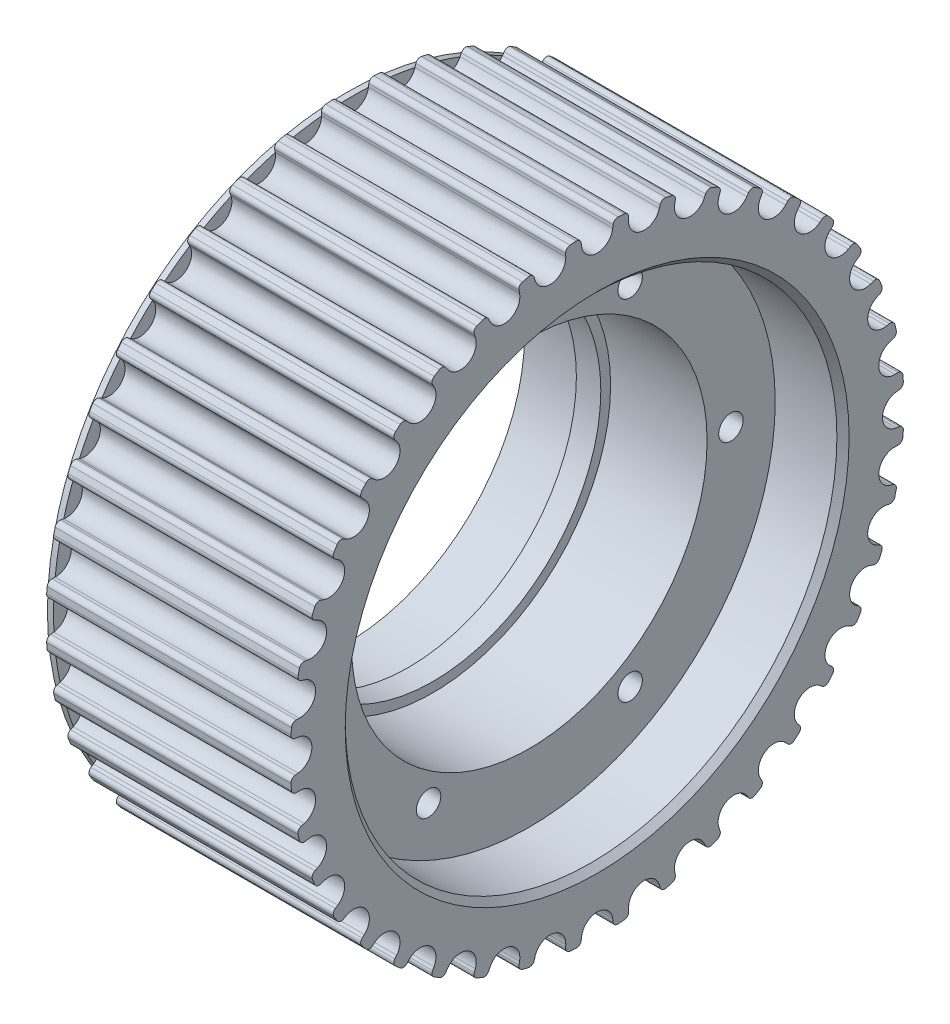
SolidWorks part; units mm, degrees
ref_plane "前视基准面" through (0, 0, 0) normal (0, 0, 1) x (1, 0, 0)
ref_plane "上视基准面" through (0, 0, 0) normal (0, 1, 0) x (1, 0, 0)
ref_plane "右视基准面" through (0, 0, 0) normal (1, 0, 0) x (0, 0, -1)
sketch "草图1" plane through (0, 0, 0) normal (0, 0, 1) x (1, 0, 0)
  line L0 (0, 0) -> (64.8368, 0) construction
  line L1 (0, 10.0488) -> (0, 50.244)
  line L2 (0, 50.244) -> (28, 50.244)
  line L3 (28, 50.244) -> (28, 20.0976)
  line L4 (28, 20.0976) -> (20, 20.0976)
  line L5 (20, 20.0976) -> (20, 10.0488)
  line L6 (20, 10.0488) -> (0, 10.0488)
  dimension "L" = 20
  dimension "B" = 28
  dimension "d" = 20.0976
  dimension "d1" = 40.1952
  dimension "da" = 100.488
revolve "旋转1" add sketch "草图1" angle 360 about L0
chamfer "倒角1" distance 1 angle 45 2 edges at (20, 0, 10.0488) (0, 0, 10.0488)
sketch "草图4" plane through (0, 0, 0) normal (-1, 0, 0) x (0, 0, 1)
  line L1 (-3, 9.5905) -> (3, 9.5905)
  line L2 (-3, 9.5905) -> (-3, 12.3905)
  line L3 (-3, 12.3905) -> (3, 12.3905)
  line L4 (3, 9.5905) -> (3, 12.3905)
  circle A0 centre (0, 0) radius 10.0488 construction
  dimension "键槽宽度" = 6
  dimension "t1" = 2.8
extrude "切除-拉伸1" cut sketch "草图4" against normal through all
ref_axis "基准轴1" through (-1.4, 0, 0) along (1, 0, 0)
sketch "草图6" plane through (0, 0, 0) normal (1, 0, 0) x (0, 0, -1)
  line L0 (0, 0) -> (0, 30.6512) construction
  line L1 (2.6101, 49.4431) -> (2.5508, 48.9608)
  line L2 (4.2154, 50.0669) -> (4.412, 51.6684)
  line L3 (-4.2154, 50.0669) -> (-4.412, 51.6684)
  line L4 (-2.6101, 49.4431) -> (-2.5508, 48.9608)
  circle A0 centre (0, 0) radius 50.244 construction
  circle A1 centre (0, 0) radius 46.704 construction
  arc A2 (-2.5508, 48.9608) -> (2.5508, 48.9608) centre (0, 49.274) ccw
  arc A3 (4.412, 51.6684) -> (-4.412, 51.6684) centre (0, 0) ccw
  arc A4 (2.6101, 49.4431) -> (3.4376, 50.1263) centre (3.3843, 49.3481) cw
  arc A5 (3.4376, 50.1263) -> (4.2154, 50.0669) centre (0, 0) cw
  arc A6 (-3.4376, 50.1263) -> (-4.2154, 50.0669) centre (0, 0) ccw
  arc A7 (-2.6101, 49.4431) -> (-3.4376, 50.1263) centre (-3.3843, 49.3481) ccw
  point P7 (0, 5.35)
  point P8 (0, 27.1112)
  point P15 (2.6995, 50.1714)
  dimension "D1" = 93.408
  dimension "ra" = 0.78
  dimension "rf" = 2.57
  dimension "hg" = 3.54
  dimension "D3" = 0.78
  dimension "D4" = 1.6136
  dimension "angle" = 14
  dimension "bw" = 5.35
extrude "切除-拉伸2" cut sketch "草图6" along normal up to next
pattern_circular "阵列(圆周)3" count 40 over 360 about axis through (-1.4, 0, 0) along (1, 0, 0) of "切除-拉伸2"
sketch "草图7" plane through (0, 0, 0) normal (-1, 0, 0) x (0, 0, 1)
  line L80 (-5.1567, 49.2427) -> (-5.1397, 48.757)
  line L81 (-10.1786, 47.959) -> (-10.3125, 48.4261)
  line L82 (-12.7965, 47.8298) -> (-12.7037, 47.3527)
  line L83 (-17.5557, 45.7762) -> (-17.7611, 46.2167)
  line L84 (-20.1211, 45.2391) -> (-19.9549, 44.7824)
  line L85 (-24.5006, 42.4663) -> (-24.7723, 42.8692)
  line L86 (-26.9504, 41.5345) -> (-26.7148, 41.1095)
  line L87 (-30.8421, 38.1108) -> (-31.1735, 38.4662)
  line L88 (-33.116, 36.8072) -> (-32.8168, 36.4242)
  line L89 (-36.4242, 32.8168) -> (-36.8072, 33.116)
  line L90 (-38.4662, 31.1735) -> (-38.1108, 30.8421)
  line L91 (-41.1095, 26.7148) -> (-41.5345, 26.9504)
  line L92 (-42.8692, 24.7723) -> (-42.4663, 24.5006)
  line L93 (-44.7824, 19.9549) -> (-45.2391, 20.1211)
  line L94 (-46.2167, 17.7611) -> (-45.7762, 17.5557)
  line L95 (-47.3527, 12.7037) -> (-47.8298, 12.7965)
  line L96 (-48.4261, 10.3125) -> (-47.959, 10.1786)
  line L97 (-48.757, 5.1397) -> (-49.2427, 5.1567)
  line L98 (-49.4431, 2.6101) -> (-48.9608, 2.5508)
  line L99 (-48.9608, -2.5508) -> (-49.4431, -2.6101)
  line L100 (-49.2427, -5.1567) -> (-48.757, -5.1397)
  line L101 (-47.959, -10.1786) -> (-48.4261, -10.3125)
  line L102 (-47.8298, -12.7965) -> (-47.3527, -12.7037)
  line L103 (-45.7762, -17.5557) -> (-46.2167, -17.7611)
  line L104 (-45.2391, -20.1211) -> (-44.7824, -19.9549)
  line L105 (-42.4663, -24.5006) -> (-42.8692, -24.7723)
  line L106 (-41.5345, -26.9504) -> (-41.1095, -26.7148)
  line L107 (-38.1108, -30.8421) -> (-38.4662, -31.1735)
  line L108 (-36.8072, -33.116) -> (-36.4242, -32.8168)
  line L109 (-32.8168, -36.4242) -> (-33.116, -36.8072)
  line L110 (-31.1735, -38.4662) -> (-30.8421, -38.1108)
  line L111 (-26.7148, -41.1095) -> (-26.9504, -41.5345)
  line L112 (-24.7723, -42.8692) -> (-24.5006, -42.4663)
  line L113 (-19.9549, -44.7824) -> (-20.1211, -45.2391)
  line L114 (-17.7611, -46.2167) -> (-17.5557, -45.7762)
  line L115 (-12.7037, -47.3527) -> (-12.7965, -47.8298)
  line L116 (-10.3125, -48.4261) -> (-10.1786, -47.959)
  line L117 (-5.1397, -48.757) -> (-5.1567, -49.2427)
  line L118 (-2.6101, -49.4431) -> (-2.5508, -48.9608)
  line L119 (2.5508, -48.9608) -> (2.6101, -49.4431)
  line L120 (5.1567, -49.2427) -> (5.1397, -48.757)
  line L121 (10.1786, -47.959) -> (10.3125, -48.4261)
  line L122 (12.7965, -47.8298) -> (12.7037, -47.3527)
  line L123 (17.5557, -45.7762) -> (17.7611, -46.2167)
  line L124 (20.1211, -45.2391) -> (19.9549, -44.7824)
  line L125 (24.5006, -42.4663) -> (24.7723, -42.8692)
  line L126 (26.9504, -41.5345) -> (26.7148, -41.1095)
  line L127 (30.8421, -38.1108) -> (31.1735, -38.4662)
  line L128 (33.116, -36.8072) -> (32.8168, -36.4242)
  line L129 (36.4242, -32.8168) -> (36.8072, -33.116)
  line L130 (38.4662, -31.1735) -> (38.1108, -30.8421)
  line L131 (41.1095, -26.7148) -> (41.5345, -26.9504)
  line L132 (42.8692, -24.7723) -> (42.4663, -24.5006)
  line L133 (44.7824, -19.9549) -> (45.2391, -20.1211)
  line L134 (46.2167, -17.7611) -> (45.7762, -17.5557)
  line L135 (47.3527, -12.7037) -> (47.8298, -12.7965)
  line L136 (48.4261, -10.3125) -> (47.959, -10.1786)
  line L137 (48.757, -5.1397) -> (49.2427, -5.1567)
  line L138 (49.4431, -2.6101) -> (48.9608, -2.5508)
  line L139 (48.9608, 2.5508) -> (49.4431, 2.6101)
  line L140 (49.2427, 5.1567) -> (48.757, 5.1397)
  line L141 (47.959, 10.1786) -> (48.4261, 10.3125)
  line L142 (47.8298, 12.7965) -> (47.3527, 12.7037)
  line L143 (45.7762, 17.5557) -> (46.2167, 17.7611)
  line L144 (45.2391, 20.1211) -> (44.7824, 19.9549)
  line L145 (42.4663, 24.5006) -> (42.8692, 24.7723)
  line L146 (41.5345, 26.9504) -> (41.1095, 26.7148)
  line L147 (38.1108, 30.8421) -> (38.4662, 31.1735)
  line L148 (36.8072, 33.116) -> (36.4242, 32.8168)
  line L149 (32.8168, 36.4242) -> (33.116, 36.8072)
  line L150 (31.1735, 38.4662) -> (30.8421, 38.1108)
  line L151 (26.7148, 41.1095) -> (26.9504, 41.5345)
  line L152 (24.7723, 42.8692) -> (24.5006, 42.4663)
  line L153 (19.9549, 44.7824) -> (20.1211, 45.2391)
  line L154 (17.7611, 46.2167) -> (17.5557, 45.7762)
  line L155 (12.7037, 47.3527) -> (12.7965, 47.8298)
  line L156 (10.3125, 48.4261) -> (10.1786, 47.959)
  line L157 (5.1397, 48.757) -> (5.1567, 49.2427)
  line L158 (2.6101, 49.4431) -> (2.5508, 48.9608)
  line L159 (-2.5508, 48.9608) -> (-2.6101, 49.4431)
  line L160 (-5.1567, 49.2427) -> (-5.1397, 48.757)
  line L161 (-10.1786, 47.959) -> (-10.3125, 48.4261)
  line L162 (-12.7965, 47.8298) -> (-12.7037, 47.3527)
  line L163 (-17.5557, 45.7762) -> (-17.7611, 46.2167)
  line L164 (-20.1211, 45.2391) -> (-19.9549, 44.7824)
  line L165 (-24.5006, 42.4663) -> (-24.7723, 42.8692)
  line L166 (-26.9504, 41.5345) -> (-26.7148, 41.1095)
  line L167 (-30.8421, 38.1108) -> (-31.1735, 38.4662)
  line L168 (-33.116, 36.8072) -> (-32.8168, 36.4242)
  line L169 (-36.4242, 32.8168) -> (-36.8072, 33.116)
  line L170 (-38.4662, 31.1735) -> (-38.1108, 30.8421)
  line L171 (-41.1095, 26.7148) -> (-41.5345, 26.9504)
  line L172 (-42.8692, 24.7723) -> (-42.4663, 24.5006)
  line L173 (-44.7824, 19.9549) -> (-45.2391, 20.1211)
  line L174 (-46.2167, 17.7611) -> (-45.7762, 17.5557)
  line L175 (-47.3527, 12.7037) -> (-47.8298, 12.7965)
  line L176 (-48.4261, 10.3125) -> (-47.959, 10.1786)
  line L177 (-48.757, 5.1397) -> (-49.2427, 5.1567)
  line L178 (-49.4431, 2.6101) -> (-48.9608, 2.5508)
  line L179 (-48.9608, -2.5508) -> (-49.4431, -2.6101)
  line L180 (-49.2427, -5.1567) -> (-48.757, -5.1397)
  line L181 (-47.959, -10.1786) -> (-48.4261, -10.3125)
  line L182 (-47.8298, -12.7965) -> (-47.3527, -12.7037)
  line L183 (-45.7762, -17.5557) -> (-46.2167, -17.7611)
  line L184 (-45.2391, -20.1211) -> (-44.7824, -19.9549)
  line L185 (-42.4663, -24.5006) -> (-42.8692, -24.7723)
  line L186 (-41.5345, -26.9504) -> (-41.1095, -26.7148)
  line L187 (-38.1108, -30.8421) -> (-38.4662, -31.1735)
  line L188 (-36.8072, -33.116) -> (-36.4242, -32.8168)
  line L189 (-32.8168, -36.4242) -> (-33.116, -36.8072)
  line L190 (-31.1735, -38.4662) -> (-30.8421, -38.1108)
  line L191 (-26.7148, -41.1095) -> (-26.9504, -41.5345)
  line L192 (-24.7723, -42.8692) -> (-24.5006, -42.4663)
  line L193 (-19.9549, -44.7824) -> (-20.1211, -45.2391)
  line L194 (-17.7611, -46.2167) -> (-17.5557, -45.7762)
  line L195 (-12.7037, -47.3527) -> (-12.7965, -47.8298)
  line L196 (-10.3125, -48.4261) -> (-10.1786, -47.959)
  line L197 (-5.1397, -48.757) -> (-5.1567, -49.2427)
  line L198 (-2.6101, -49.4431) -> (-2.5508, -48.9608)
  line L199 (2.5508, -48.9608) -> (2.6101, -49.4431)
  line L200 (5.1567, -49.2427) -> (5.1397, -48.757)
  line L201 (10.1786, -47.959) -> (10.3125, -48.4261)
  line L202 (12.7965, -47.8298) -> (12.7037, -47.3527)
  line L203 (17.5557, -45.7762) -> (17.7611, -46.2167)
  line L204 (20.1211, -45.2391) -> (19.9549, -44.7824)
  line L205 (24.5006, -42.4663) -> (24.7723, -42.8692)
  line L206 (26.9504, -41.5345) -> (26.7148, -41.1095)
  line L207 (30.8421, -38.1108) -> (31.1735, -38.4662)
  line L208 (33.116, -36.8072) -> (32.8168, -36.4242)
  line L209 (36.4242, -32.8168) -> (36.8072, -33.116)
  line L210 (38.4662, -31.1735) -> (38.1108, -30.8421)
  line L211 (41.1095, -26.7148) -> (41.5345, -26.9504)
  line L212 (42.8692, -24.7723) -> (42.4663, -24.5006)
  line L213 (44.7824, -19.9549) -> (45.2391, -20.1211)
  line L214 (46.2167, -17.7611) -> (45.7762, -17.5557)
  line L215 (47.3527, -12.7037) -> (47.8298, -12.7965)
  line L216 (48.4261, -10.3125) -> (47.959, -10.1786)
  line L217 (48.757, -5.1397) -> (49.2427, -5.1567)
  line L218 (49.4431, -2.6101) -> (48.9608, -2.5508)
  line L219 (48.9608, 2.5508) -> (49.4431, 2.6101)
  line L220 (49.2427, 5.1567) -> (48.757, 5.1397)
  line L221 (47.959, 10.1786) -> (48.4261, 10.3125)
  line L222 (47.8298, 12.7965) -> (47.3527, 12.7037)
  line L223 (45.7762, 17.5557) -> (46.2167, 17.7611)
  line L224 (45.2391, 20.1211) -> (44.7824, 19.9549)
  line L225 (42.4663, 24.5006) -> (42.8692, 24.7723)
  line L226 (41.5345, 26.9504) -> (41.1095, 26.7148)
  line L227 (38.1108, 30.8421) -> (38.4662, 31.1735)
  line L228 (36.8072, 33.116) -> (36.4242, 32.8168)
  line L229 (32.8168, 36.4242) -> (33.116, 36.8072)
  line L230 (31.1735, 38.4662) -> (30.8421, 38.1108)
  line L231 (26.7148, 41.1095) -> (26.9504, 41.5345)
  line L232 (24.7723, 42.8692) -> (24.5006, 42.4663)
  line L233 (19.9549, 44.7824) -> (20.1211, 45.2391)
  line L234 (17.7611, 46.2167) -> (17.5557, 45.7762)
  line L235 (12.7037, 47.3527) -> (12.7965, 47.8298)
  line L236 (10.3125, 48.4261) -> (10.1786, 47.959)
  line L237 (5.1397, 48.757) -> (5.1567, 49.2427)
  line L238 (2.6101, 49.4431) -> (2.5508, 48.9608)
  line L239 (-2.5508, 48.9608) -> (-2.6101, 49.4431)
  arc A160 (-4.4462, 50.0469) -> (-5.1567, 49.2427) centre (-4.3772, 49.2699) ccw
  arc A161 (-10.1786, 47.959) -> (-5.1397, 48.757) centre (-7.7082, 48.6674) ccw
  arc A162 (-10.3125, 48.4261) -> (-11.2368, 48.9714) centre (-11.0623, 48.2111) ccw
  arc A163 (-11.2368, 48.9714) -> (-12.2205, 48.7352) centre (0, 0) ccw
  arc A164 (-12.2205, 48.7352) -> (-12.7965, 47.8298) centre (-12.0308, 47.9786) ccw
  arc A165 (-17.5557, 45.7762) -> (-12.7037, 47.3527) centre (-15.2265, 46.8624) ccw
  arc A166 (-17.7611, 46.2167) -> (-18.7592, 46.6106) centre (-18.468, 45.887) ccw
  arc A167 (-18.7592, 46.6106) -> (-19.6939, 46.2235) centre (0, 0) ccw
  arc A168 (-19.6939, 46.2235) -> (-20.1211, 45.2391) centre (-19.3882, 45.5059) ccw
  arc A169 (-24.5006, 42.4663) -> (-19.9549, 44.7824) centre (-22.3699, 43.9035) ccw
  arc A170 (-24.7723, 42.8692) -> (-25.8198, 43.1022) centre (-25.419, 42.4331) ccw
  arc A171 (-25.8198, 43.1022) -> (-26.6824, 42.5736) centre (0, 0) ccw
  arc A172 (-26.6824, 42.5736) -> (-26.9504, 41.5345) centre (-26.2682, 41.9127) ccw
  arc A173 (-30.8421, 38.1108) -> (-26.7148, 41.1095) centre (-28.9625, 39.8635) ccw
  arc A174 (-31.1735, 38.4662) -> (-32.2446, 38.5324) centre (-31.744, 37.9342) ccw
  arc A175 (-32.2446, 38.5324) -> (-33.0139, 37.8754) centre (0, 0) ccw
  arc A176 (-33.0139, 37.8754) -> (-33.116, 36.8072) centre (-32.5013, 37.2874) ccw
  arc A177 (-36.4242, 32.8168) -> (-32.8168, 36.4242) centre (-34.842, 34.842) ccw
  arc A178 (-36.8072, 33.116) -> (-37.8754, 33.0139) centre (-37.2874, 32.5013) ccw
  arc A179 (-37.8754, 33.0139) -> (-38.5324, 32.2446) centre (0, 0) ccw
  arc A180 (-38.5324, 32.2446) -> (-38.4662, 31.1735) centre (-37.9342, 31.744) ccw
  arc A181 (-41.1095, 26.7148) -> (-38.1108, 30.8421) centre (-39.8635, 28.9625) ccw
  arc A182 (-41.5345, 26.9504) -> (-42.5736, 26.6824) centre (-41.9127, 26.2682) ccw
  arc A183 (-42.5736, 26.6824) -> (-43.1022, 25.8198) centre (0, 0) ccw
  arc A184 (-43.1022, 25.8198) -> (-42.8692, 24.7723) centre (-42.4331, 25.419) ccw
  arc A185 (-44.7824, 19.9549) -> (-42.4663, 24.5006) centre (-43.9035, 22.3699) ccw
  arc A186 (-45.2391, 20.1211) -> (-46.2235, 19.6939) centre (-45.5059, 19.3882) ccw
  arc A187 (-46.2235, 19.6939) -> (-46.6106, 18.7592) centre (0, 0) ccw
  arc A188 (-46.6106, 18.7592) -> (-46.2167, 17.7611) centre (-45.887, 18.468) ccw
  arc A189 (-47.3527, 12.7037) -> (-45.7762, 17.5557) centre (-46.8624, 15.2265) ccw
  arc A190 (-47.8298, 12.7965) -> (-48.7352, 12.2205) centre (-47.9786, 12.0308) ccw
  arc A191 (-48.7352, 12.2205) -> (-48.9714, 11.2368) centre (0, 0) ccw
  arc A192 (-48.9714, 11.2368) -> (-48.4261, 10.3125) centre (-48.2111, 11.0623) ccw
  arc A193 (-48.757, 5.1397) -> (-47.959, 10.1786) centre (-48.6674, 7.7082) ccw
  arc A194 (-49.2427, 5.1567) -> (-50.0469, 4.4462) centre (-49.2699, 4.3772) ccw
  arc A195 (-50.0469, 4.4462) -> (-50.1263, 3.4376) centre (0, 0) ccw
  arc A196 (-50.1263, 3.4376) -> (-49.4431, 2.6101) centre (-49.3481, 3.3843) ccw
  arc A197 (-48.9608, -2.5508) -> (-48.9608, 2.5508) centre (-49.274, 0) ccw
  arc A198 (-49.4431, -2.6101) -> (-50.1263, -3.4376) centre (-49.3481, -3.3843) ccw
  arc A199 (-50.1263, -3.4376) -> (-50.0469, -4.4462) centre (0, 0) ccw
  arc A200 (-50.0469, -4.4462) -> (-49.2427, -5.1567) centre (-49.2699, -4.3772) ccw
  arc A201 (-47.959, -10.1786) -> (-48.757, -5.1397) centre (-48.6674, -7.7082) ccw
  arc A202 (-48.4261, -10.3125) -> (-48.9714, -11.2368) centre (-48.2111, -11.0623) ccw
  arc A203 (-48.9714, -11.2368) -> (-48.7352, -12.2205) centre (0, 0) ccw
  arc A204 (-48.7352, -12.2205) -> (-47.8298, -12.7965) centre (-47.9786, -12.0308) ccw
  arc A205 (-45.7762, -17.5557) -> (-47.3527, -12.7037) centre (-46.8624, -15.2265) ccw
  arc A206 (-46.2167, -17.7611) -> (-46.6106, -18.7592) centre (-45.887, -18.468) ccw
  arc A207 (-46.6106, -18.7592) -> (-46.2235, -19.6939) centre (0, 0) ccw
  arc A208 (-46.2235, -19.6939) -> (-45.2391, -20.1211) centre (-45.5059, -19.3882) ccw
  arc A209 (-42.4663, -24.5006) -> (-44.7824, -19.9549) centre (-43.9035, -22.3699) ccw
  arc A210 (-42.8692, -24.7723) -> (-43.1022, -25.8198) centre (-42.4331, -25.419) ccw
  arc A211 (-43.1022, -25.8198) -> (-42.5736, -26.6824) centre (0, 0) ccw
  arc A212 (-42.5736, -26.6824) -> (-41.5345, -26.9504) centre (-41.9127, -26.2682) ccw
  arc A213 (-38.1108, -30.8421) -> (-41.1095, -26.7148) centre (-39.8635, -28.9625) ccw
  arc A214 (-38.4662, -31.1735) -> (-38.5324, -32.2446) centre (-37.9342, -31.744) ccw
  arc A215 (-38.5324, -32.2446) -> (-37.8754, -33.0139) centre (0, 0) ccw
  arc A216 (-37.8754, -33.0139) -> (-36.8072, -33.116) centre (-37.2874, -32.5013) ccw
  arc A217 (-32.8168, -36.4242) -> (-36.4242, -32.8168) centre (-34.842, -34.842) ccw
  arc A218 (-33.116, -36.8072) -> (-33.0139, -37.8754) centre (-32.5013, -37.2874) ccw
  arc A219 (-33.0139, -37.8754) -> (-32.2446, -38.5324) centre (0, 0) ccw
  arc A220 (-32.2446, -38.5324) -> (-31.1735, -38.4662) centre (-31.744, -37.9342) ccw
  arc A221 (-26.7148, -41.1095) -> (-30.8421, -38.1108) centre (-28.9625, -39.8635) ccw
  arc A222 (-26.9504, -41.5345) -> (-26.6824, -42.5736) centre (-26.2682, -41.9127) ccw
  arc A223 (-26.6824, -42.5736) -> (-25.8198, -43.1022) centre (0, 0) ccw
  arc A224 (-25.8198, -43.1022) -> (-24.7723, -42.8692) centre (-25.419, -42.4331) ccw
  arc A225 (-19.9549, -44.7824) -> (-24.5006, -42.4663) centre (-22.3699, -43.9035) ccw
  arc A226 (-20.1211, -45.2391) -> (-19.6939, -46.2235) centre (-19.3882, -45.5059) ccw
  arc A227 (-19.6939, -46.2235) -> (-18.7592, -46.6106) centre (0, 0) ccw
  arc A228 (-18.7592, -46.6106) -> (-17.7611, -46.2167) centre (-18.468, -45.887) ccw
  arc A229 (-12.7037, -47.3527) -> (-17.5557, -45.7762) centre (-15.2265, -46.8624) ccw
  arc A230 (-12.7965, -47.8298) -> (-12.2205, -48.7352) centre (-12.0308, -47.9786) ccw
  arc A231 (-12.2205, -48.7352) -> (-11.2368, -48.9714) centre (0, 0) ccw
  arc A232 (-11.2368, -48.9714) -> (-10.3125, -48.4261) centre (-11.0623, -48.2111) ccw
  arc A233 (-5.1397, -48.757) -> (-10.1786, -47.959) centre (-7.7082, -48.6674) ccw
  arc A234 (-5.1567, -49.2427) -> (-4.4462, -50.0469) centre (-4.3772, -49.2699) ccw
  arc A235 (-4.4462, -50.0469) -> (-3.4376, -50.1263) centre (0, 0) ccw
  arc A236 (-3.4376, -50.1263) -> (-2.6101, -49.4431) centre (-3.3843, -49.3481) ccw
  arc A237 (2.5508, -48.9608) -> (-2.5508, -48.9608) centre (0, -49.274) ccw
  arc A238 (2.6101, -49.4431) -> (3.4376, -50.1263) centre (3.3843, -49.3481) ccw
  arc A239 (3.4376, -50.1263) -> (4.4462, -50.0469) centre (0, 0) ccw
  arc A240 (4.4462, -50.0469) -> (5.1567, -49.2427) centre (4.3772, -49.2699) ccw
  arc A241 (10.1786, -47.959) -> (5.1397, -48.757) centre (7.7082, -48.6674) ccw
  arc A242 (10.3125, -48.4261) -> (11.2368, -48.9714) centre (11.0623, -48.2111) ccw
  arc A243 (11.2368, -48.9714) -> (12.2205, -48.7352) centre (0, 0) ccw
  arc A244 (12.2205, -48.7352) -> (12.7965, -47.8298) centre (12.0308, -47.9786) ccw
  arc A245 (17.5557, -45.7762) -> (12.7037, -47.3527) centre (15.2265, -46.8624) ccw
  arc A246 (17.7611, -46.2167) -> (18.7592, -46.6106) centre (18.468, -45.887) ccw
  arc A247 (18.7592, -46.6106) -> (19.6939, -46.2235) centre (0, 0) ccw
  arc A248 (19.6939, -46.2235) -> (20.1211, -45.2391) centre (19.3882, -45.5059) ccw
  arc A249 (24.5006, -42.4663) -> (19.9549, -44.7824) centre (22.3699, -43.9035) ccw
  arc A250 (24.7723, -42.8692) -> (25.8198, -43.1022) centre (25.419, -42.4331) ccw
  arc A251 (25.8198, -43.1022) -> (26.6824, -42.5736) centre (0, 0) ccw
  arc A252 (26.6824, -42.5736) -> (26.9504, -41.5345) centre (26.2682, -41.9127) ccw
  arc A253 (30.8421, -38.1108) -> (26.7148, -41.1095) centre (28.9625, -39.8635) ccw
  arc A254 (31.1735, -38.4662) -> (32.2446, -38.5324) centre (31.744, -37.9342) ccw
  arc A255 (32.2446, -38.5324) -> (33.0139, -37.8754) centre (0, 0) ccw
  arc A256 (33.0139, -37.8754) -> (33.116, -36.8072) centre (32.5013, -37.2874) ccw
  arc A257 (36.4242, -32.8168) -> (32.8168, -36.4242) centre (34.842, -34.842) ccw
  arc A258 (36.8072, -33.116) -> (37.8754, -33.0139) centre (37.2874, -32.5013) ccw
  arc A259 (37.8754, -33.0139) -> (38.5324, -32.2446) centre (0, 0) ccw
  arc A260 (38.5324, -32.2446) -> (38.4662, -31.1735) centre (37.9342, -31.744) ccw
  arc A261 (41.1095, -26.7148) -> (38.1108, -30.8421) centre (39.8635, -28.9625) ccw
  arc A262 (41.5345, -26.9504) -> (42.5736, -26.6824) centre (41.9127, -26.2682) ccw
  arc A263 (42.5736, -26.6824) -> (43.1022, -25.8198) centre (0, 0) ccw
  arc A264 (43.1022, -25.8198) -> (42.8692, -24.7723) centre (42.4331, -25.419) ccw
  arc A265 (44.7824, -19.9549) -> (42.4663, -24.5006) centre (43.9035, -22.3699) ccw
  arc A266 (45.2391, -20.1211) -> (46.2235, -19.6939) centre (45.5059, -19.3882) ccw
  arc A267 (46.2235, -19.6939) -> (46.6106, -18.7592) centre (0, 0) ccw
  arc A268 (46.6106, -18.7592) -> (46.2167, -17.7611) centre (45.887, -18.468) ccw
  arc A269 (47.3527, -12.7037) -> (45.7762, -17.5557) centre (46.8624, -15.2265) ccw
  arc A270 (47.8298, -12.7965) -> (48.7352, -12.2205) centre (47.9786, -12.0308) ccw
  arc A271 (48.7352, -12.2205) -> (48.9714, -11.2368) centre (0, 0) ccw
  arc A272 (48.9714, -11.2368) -> (48.4261, -10.3125) centre (48.2111, -11.0623) ccw
  arc A273 (48.757, -5.1397) -> (47.959, -10.1786) centre (48.6674, -7.7082) ccw
  arc A274 (49.2427, -5.1567) -> (50.0469, -4.4462) centre (49.2699, -4.3772) ccw
  arc A275 (50.0469, -4.4462) -> (50.1263, -3.4376) centre (0, 0) ccw
  arc A276 (50.1263, -3.4376) -> (49.4431, -2.6101) centre (49.3481, -3.3843) ccw
  arc A277 (48.9608, 2.5508) -> (48.9608, -2.5508) centre (49.274, 0) ccw
  arc A278 (49.4431, 2.6101) -> (50.1263, 3.4376) centre (49.3481, 3.3843) ccw
  arc A279 (50.1263, 3.4376) -> (50.0469, 4.4462) centre (0, 0) ccw
  arc A280 (50.0469, 4.4462) -> (49.2427, 5.1567) centre (49.2699, 4.3772) ccw
  arc A281 (47.959, 10.1786) -> (48.757, 5.1397) centre (48.6674, 7.7082) ccw
  arc A282 (48.4261, 10.3125) -> (48.9714, 11.2368) centre (48.2111, 11.0623) ccw
  arc A283 (48.9714, 11.2368) -> (48.7352, 12.2205) centre (0, 0) ccw
  arc A284 (48.7352, 12.2205) -> (47.8298, 12.7965) centre (47.9786, 12.0308) ccw
  arc A285 (45.7762, 17.5557) -> (47.3527, 12.7037) centre (46.8624, 15.2265) ccw
  arc A286 (46.2167, 17.7611) -> (46.6106, 18.7592) centre (45.887, 18.468) ccw
  arc A287 (46.6106, 18.7592) -> (46.2235, 19.6939) centre (0, 0) ccw
  arc A288 (46.2235, 19.6939) -> (45.2391, 20.1211) centre (45.5059, 19.3882) ccw
  arc A289 (42.4663, 24.5006) -> (44.7824, 19.9549) centre (43.9035, 22.3699) ccw
  arc A290 (42.8692, 24.7723) -> (43.1022, 25.8198) centre (42.4331, 25.419) ccw
  arc A291 (43.1022, 25.8198) -> (42.5736, 26.6824) centre (0, 0) ccw
  arc A292 (42.5736, 26.6824) -> (41.5345, 26.9504) centre (41.9127, 26.2682) ccw
  arc A293 (38.1108, 30.8421) -> (41.1095, 26.7148) centre (39.8635, 28.9625) ccw
  arc A294 (38.4662, 31.1735) -> (38.5324, 32.2446) centre (37.9342, 31.744) ccw
  arc A295 (38.5324, 32.2446) -> (37.8754, 33.0139) centre (0, 0) ccw
  arc A296 (37.8754, 33.0139) -> (36.8072, 33.116) centre (37.2874, 32.5013) ccw
  arc A297 (32.8168, 36.4242) -> (36.4242, 32.8168) centre (34.842, 34.842) ccw
  arc A298 (33.116, 36.8072) -> (33.0139, 37.8754) centre (32.5013, 37.2874) ccw
  arc A299 (33.0139, 37.8754) -> (32.2446, 38.5324) centre (0, 0) ccw
  arc A300 (32.2446, 38.5324) -> (31.1735, 38.4662) centre (31.744, 37.9342) ccw
  arc A301 (26.7148, 41.1095) -> (30.8421, 38.1108) centre (28.9625, 39.8635) ccw
  arc A302 (26.9504, 41.5345) -> (26.6824, 42.5736) centre (26.2682, 41.9127) ccw
  arc A303 (26.6824, 42.5736) -> (25.8198, 43.1022) centre (0, 0) ccw
  arc A304 (25.8198, 43.1022) -> (24.7723, 42.8692) centre (25.419, 42.4331) ccw
  arc A305 (19.9549, 44.7824) -> (24.5006, 42.4663) centre (22.3699, 43.9035) ccw
  arc A306 (20.1211, 45.2391) -> (19.6939, 46.2235) centre (19.3882, 45.5059) ccw
  arc A307 (19.6939, 46.2235) -> (18.7592, 46.6106) centre (0, 0) ccw
  arc A308 (18.7592, 46.6106) -> (17.7611, 46.2167) centre (18.468, 45.887) ccw
  arc A309 (12.7037, 47.3527) -> (17.5557, 45.7762) centre (15.2265, 46.8624) ccw
  arc A310 (12.7965, 47.8298) -> (12.2205, 48.7352) centre (12.0308, 47.9786) ccw
  arc A311 (12.2205, 48.7352) -> (11.2368, 48.9714) centre (0, 0) ccw
  arc A312 (11.2368, 48.9714) -> (10.3125, 48.4261) centre (11.0623, 48.2111) ccw
  arc A313 (5.1397, 48.757) -> (10.1786, 47.959) centre (7.7082, 48.6674) ccw
  arc A314 (5.1567, 49.2427) -> (4.4462, 50.0469) centre (4.3772, 49.2699) ccw
  arc A315 (4.4462, 50.0469) -> (3.4376, 50.1263) centre (0, 0) ccw
  arc A316 (3.4376, 50.1263) -> (2.6101, 49.4431) centre (3.3843, 49.3481) ccw
  arc A317 (-2.5508, 48.9608) -> (2.5508, 48.9608) centre (0, 49.274) ccw
  arc A318 (-2.6101, 49.4431) -> (-3.4376, 50.1263) centre (-3.3843, 49.3481) ccw
  arc A319 (-3.4376, 50.1263) -> (-4.4462, 50.0469) centre (0, 0) ccw
  arc A320 (-4.4462, 50.0469) -> (-5.1567, 49.2427) centre (-4.3772, 49.2699) ccw
  arc A321 (-10.1786, 47.959) -> (-5.1397, 48.757) centre (-7.7082, 48.6674) ccw
  arc A322 (-10.3125, 48.4261) -> (-11.2368, 48.9714) centre (-11.0623, 48.2111) ccw
  arc A323 (-11.2368, 48.9714) -> (-12.2205, 48.7352) centre (0, 0) ccw
  arc A324 (-12.2205, 48.7352) -> (-12.7965, 47.8298) centre (-12.0308, 47.9786) ccw
  arc A325 (-17.5557, 45.7762) -> (-12.7037, 47.3527) centre (-15.2265, 46.8624) ccw
  arc A326 (-17.7611, 46.2167) -> (-18.7592, 46.6106) centre (-18.468, 45.887) ccw
  arc A327 (-18.7592, 46.6106) -> (-19.6939, 46.2235) centre (0, 0) ccw
  arc A328 (-19.6939, 46.2235) -> (-20.1211, 45.2391) centre (-19.3882, 45.5059) ccw
  arc A329 (-24.5006, 42.4663) -> (-19.9549, 44.7824) centre (-22.3699, 43.9035) ccw
  arc A330 (-24.7723, 42.8692) -> (-25.8198, 43.1022) centre (-25.419, 42.4331) ccw
  arc A331 (-25.8198, 43.1022) -> (-26.6824, 42.5736) centre (0, 0) ccw
  arc A332 (-26.6824, 42.5736) -> (-26.9504, 41.5345) centre (-26.2682, 41.9127) ccw
  arc A333 (-30.8421, 38.1108) -> (-26.7148, 41.1095) centre (-28.9625, 39.8635) ccw
  arc A334 (-31.1735, 38.4662) -> (-32.2446, 38.5324) centre (-31.744, 37.9342) ccw
  arc A335 (-32.2446, 38.5324) -> (-33.0139, 37.8754) centre (0, 0) ccw
  arc A336 (-33.0139, 37.8754) -> (-33.116, 36.8072) centre (-32.5013, 37.2874) ccw
  arc A337 (-36.4242, 32.8168) -> (-32.8168, 36.4242) centre (-34.842, 34.842) ccw
  arc A338 (-36.8072, 33.116) -> (-37.8754, 33.0139) centre (-37.2874, 32.5013) ccw
  arc A339 (-37.8754, 33.0139) -> (-38.5324, 32.2446) centre (0, 0) ccw
  arc A340 (-38.5324, 32.2446) -> (-38.4662, 31.1735) centre (-37.9342, 31.744) ccw
  arc A341 (-41.1095, 26.7148) -> (-38.1108, 30.8421) centre (-39.8635, 28.9625) ccw
  arc A342 (-41.5345, 26.9504) -> (-42.5736, 26.6824) centre (-41.9127, 26.2682) ccw
  arc A343 (-42.5736, 26.6824) -> (-43.1022, 25.8198) centre (0, 0) ccw
  arc A344 (-43.1022, 25.8198) -> (-42.8692, 24.7723) centre (-42.4331, 25.419) ccw
  arc A345 (-44.7824, 19.9549) -> (-42.4663, 24.5006) centre (-43.9035, 22.3699) ccw
  arc A346 (-45.2391, 20.1211) -> (-46.2235, 19.6939) centre (-45.5059, 19.3882) ccw
  arc A347 (-46.2235, 19.6939) -> (-46.6106, 18.7592) centre (0, 0) ccw
  arc A348 (-46.6106, 18.7592) -> (-46.2167, 17.7611) centre (-45.887, 18.468) ccw
  arc A349 (-47.3527, 12.7037) -> (-45.7762, 17.5557) centre (-46.8624, 15.2265) ccw
  arc A350 (-47.8298, 12.7965) -> (-48.7352, 12.2205) centre (-47.9786, 12.0308) ccw
  arc A351 (-48.7352, 12.2205) -> (-48.9714, 11.2368) centre (0, 0) ccw
  arc A352 (-48.9714, 11.2368) -> (-48.4261, 10.3125) centre (-48.2111, 11.0623) ccw
  arc A353 (-48.757, 5.1397) -> (-47.959, 10.1786) centre (-48.6674, 7.7082) ccw
  arc A354 (-49.2427, 5.1567) -> (-50.0469, 4.4462) centre (-49.2699, 4.3772) ccw
  arc A355 (-50.0469, 4.4462) -> (-50.1263, 3.4376) centre (0, 0) ccw
  arc A356 (-50.1263, 3.4376) -> (-49.4431, 2.6101) centre (-49.3481, 3.3843) ccw
  arc A357 (-48.9608, -2.5508) -> (-48.9608, 2.5508) centre (-49.274, 0) ccw
  arc A358 (-49.4431, -2.6101) -> (-50.1263, -3.4376) centre (-49.3481, -3.3843) ccw
  arc A359 (-50.1263, -3.4376) -> (-50.0469, -4.4462) centre (0, 0) ccw
  arc A360 (-50.0469, -4.4462) -> (-49.2427, -5.1567) centre (-49.2699, -4.3772) ccw
  arc A361 (-47.959, -10.1786) -> (-48.757, -5.1397) centre (-48.6674, -7.7082) ccw
  arc A362 (-48.4261, -10.3125) -> (-48.9714, -11.2368) centre (-48.2111, -11.0623) ccw
  arc A363 (-48.9714, -11.2368) -> (-48.7352, -12.2205) centre (0, 0) ccw
  arc A364 (-48.7352, -12.2205) -> (-47.8298, -12.7965) centre (-47.9786, -12.0308) ccw
  arc A365 (-45.7762, -17.5557) -> (-47.3527, -12.7037) centre (-46.8624, -15.2265) ccw
  arc A366 (-46.2167, -17.7611) -> (-46.6106, -18.7592) centre (-45.887, -18.468) ccw
  arc A367 (-46.6106, -18.7592) -> (-46.2235, -19.6939) centre (0, 0) ccw
  arc A368 (-46.2235, -19.6939) -> (-45.2391, -20.1211) centre (-45.5059, -19.3882) ccw
  arc A369 (-42.4663, -24.5006) -> (-44.7824, -19.9549) centre (-43.9035, -22.3699) ccw
  arc A370 (-42.8692, -24.7723) -> (-43.1022, -25.8198) centre (-42.4331, -25.419) ccw
  arc A371 (-43.1022, -25.8198) -> (-42.5736, -26.6824) centre (0, 0) ccw
  arc A372 (-42.5736, -26.6824) -> (-41.5345, -26.9504) centre (-41.9127, -26.2682) ccw
  arc A373 (-38.1108, -30.8421) -> (-41.1095, -26.7148) centre (-39.8635, -28.9625) ccw
  arc A374 (-38.4662, -31.1735) -> (-38.5324, -32.2446) centre (-37.9342, -31.744) ccw
  arc A375 (-38.5324, -32.2446) -> (-37.8754, -33.0139) centre (0, 0) ccw
  arc A376 (-37.8754, -33.0139) -> (-36.8072, -33.116) centre (-37.2874, -32.5013) ccw
  arc A377 (-32.8168, -36.4242) -> (-36.4242, -32.8168) centre (-34.842, -34.842) ccw
  arc A378 (-33.116, -36.8072) -> (-33.0139, -37.8754) centre (-32.5013, -37.2874) ccw
  arc A379 (-33.0139, -37.8754) -> (-32.2446, -38.5324) centre (0, 0) ccw
  arc A380 (-32.2446, -38.5324) -> (-31.1735, -38.4662) centre (-31.744, -37.9342) ccw
  arc A381 (-26.7148, -41.1095) -> (-30.8421, -38.1108) centre (-28.9625, -39.8635) ccw
  arc A382 (-26.9504, -41.5345) -> (-26.6824, -42.5736) centre (-26.2682, -41.9127) ccw
  arc A383 (-26.6824, -42.5736) -> (-25.8198, -43.1022) centre (0, 0) ccw
  arc A384 (-25.8198, -43.1022) -> (-24.7723, -42.8692) centre (-25.419, -42.4331) ccw
  arc A385 (-19.9549, -44.7824) -> (-24.5006, -42.4663) centre (-22.3699, -43.9035) ccw
  arc A386 (-20.1211, -45.2391) -> (-19.6939, -46.2235) centre (-19.3882, -45.5059) ccw
  arc A387 (-19.6939, -46.2235) -> (-18.7592, -46.6106) centre (0, 0) ccw
  arc A388 (-18.7592, -46.6106) -> (-17.7611, -46.2167) centre (-18.468, -45.887) ccw
  arc A389 (-12.7037, -47.3527) -> (-17.5557, -45.7762) centre (-15.2265, -46.8624) ccw
  arc A390 (-12.7965, -47.8298) -> (-12.2205, -48.7352) centre (-12.0308, -47.9786) ccw
  arc A391 (-12.2205, -48.7352) -> (-11.2368, -48.9714) centre (0, 0) ccw
  arc A392 (-11.2368, -48.9714) -> (-10.3125, -48.4261) centre (-11.0623, -48.2111) ccw
  arc A393 (-5.1397, -48.757) -> (-10.1786, -47.959) centre (-7.7082, -48.6674) ccw
  arc A394 (-5.1567, -49.2427) -> (-4.4462, -50.0469) centre (-4.3772, -49.2699) ccw
  arc A395 (-4.4462, -50.0469) -> (-3.4376, -50.1263) centre (0, 0) ccw
  arc A396 (-3.4376, -50.1263) -> (-2.6101, -49.4431) centre (-3.3843, -49.3481) ccw
  arc A397 (2.5508, -48.9608) -> (-2.5508, -48.9608) centre (0, -49.274) ccw
  arc A398 (2.6101, -49.4431) -> (3.4376, -50.1263) centre (3.3843, -49.3481) ccw
  arc A399 (3.4376, -50.1263) -> (4.4462, -50.0469) centre (0, 0) ccw
  arc A400 (4.4462, -50.0469) -> (5.1567, -49.2427) centre (4.3772, -49.2699) ccw
  arc A401 (10.1786, -47.959) -> (5.1397, -48.757) centre (7.7082, -48.6674) ccw
  arc A402 (10.3125, -48.4261) -> (11.2368, -48.9714) centre (11.0623, -48.2111) ccw
  arc A403 (11.2368, -48.9714) -> (12.2205, -48.7352) centre (0, 0) ccw
  arc A404 (12.2205, -48.7352) -> (12.7965, -47.8298) centre (12.0308, -47.9786) ccw
  arc A405 (17.5557, -45.7762) -> (12.7037, -47.3527) centre (15.2265, -46.8624) ccw
  arc A406 (17.7611, -46.2167) -> (18.7592, -46.6106) centre (18.468, -45.887) ccw
  arc A407 (18.7592, -46.6106) -> (19.6939, -46.2235) centre (0, 0) ccw
  arc A408 (19.6939, -46.2235) -> (20.1211, -45.2391) centre (19.3882, -45.5059) ccw
  arc A409 (24.5006, -42.4663) -> (19.9549, -44.7824) centre (22.3699, -43.9035) ccw
  arc A410 (24.7723, -42.8692) -> (25.8198, -43.1022) centre (25.419, -42.4331) ccw
  arc A411 (25.8198, -43.1022) -> (26.6824, -42.5736) centre (0, 0) ccw
  arc A412 (26.6824, -42.5736) -> (26.9504, -41.5345) centre (26.2682, -41.9127) ccw
  arc A413 (30.8421, -38.1108) -> (26.7148, -41.1095) centre (28.9625, -39.8635) ccw
  arc A414 (31.1735, -38.4662) -> (32.2446, -38.5324) centre (31.744, -37.9342) ccw
  arc A415 (32.2446, -38.5324) -> (33.0139, -37.8754) centre (0, 0) ccw
  arc A416 (33.0139, -37.8754) -> (33.116, -36.8072) centre (32.5013, -37.2874) ccw
  arc A417 (36.4242, -32.8168) -> (32.8168, -36.4242) centre (34.842, -34.842) ccw
  arc A418 (36.8072, -33.116) -> (37.8754, -33.0139) centre (37.2874, -32.5013) ccw
  arc A419 (37.8754, -33.0139) -> (38.5324, -32.2446) centre (0, 0) ccw
  arc A420 (38.5324, -32.2446) -> (38.4662, -31.1735) centre (37.9342, -31.744) ccw
  arc A421 (41.1095, -26.7148) -> (38.1108, -30.8421) centre (39.8635, -28.9625) ccw
  arc A422 (41.5345, -26.9504) -> (42.5736, -26.6824) centre (41.9127, -26.2682) ccw
  arc A423 (42.5736, -26.6824) -> (43.1022, -25.8198) centre (0, 0) ccw
  arc A424 (43.1022, -25.8198) -> (42.8692, -24.7723) centre (42.4331, -25.419) ccw
  arc A425 (44.7824, -19.9549) -> (42.4663, -24.5006) centre (43.9035, -22.3699) ccw
  arc A426 (45.2391, -20.1211) -> (46.2235, -19.6939) centre (45.5059, -19.3882) ccw
  arc A427 (46.2235, -19.6939) -> (46.6106, -18.7592) centre (0, 0) ccw
  arc A428 (46.6106, -18.7592) -> (46.2167, -17.7611) centre (45.887, -18.468) ccw
  arc A429 (47.3527, -12.7037) -> (45.7762, -17.5557) centre (46.8624, -15.2265) ccw
  arc A430 (47.8298, -12.7965) -> (48.7352, -12.2205) centre (47.9786, -12.0308) ccw
  arc A431 (48.7352, -12.2205) -> (48.9714, -11.2368) centre (0, 0) ccw
  arc A432 (48.9714, -11.2368) -> (48.4261, -10.3125) centre (48.2111, -11.0623) ccw
  arc A433 (48.757, -5.1397) -> (47.959, -10.1786) centre (48.6674, -7.7082) ccw
  arc A434 (49.2427, -5.1567) -> (50.0469, -4.4462) centre (49.2699, -4.3772) ccw
  arc A435 (50.0469, -4.4462) -> (50.1263, -3.4376) centre (0, 0) ccw
  arc A436 (50.1263, -3.4376) -> (49.4431, -2.6101) centre (49.3481, -3.3843) ccw
  arc A437 (48.9608, 2.5508) -> (48.9608, -2.5508) centre (49.274, 0) ccw
  arc A438 (49.4431, 2.6101) -> (50.1263, 3.4376) centre (49.3481, 3.3843) ccw
  arc A439 (50.1263, 3.4376) -> (50.0469, 4.4462) centre (0, 0) ccw
  arc A440 (50.0469, 4.4462) -> (49.2427, 5.1567) centre (49.2699, 4.3772) ccw
  arc A441 (47.959, 10.1786) -> (48.757, 5.1397) centre (48.6674, 7.7082) ccw
  arc A442 (48.4261, 10.3125) -> (48.9714, 11.2368) centre (48.2111, 11.0623) ccw
  arc A443 (48.9714, 11.2368) -> (48.7352, 12.2205) centre (0, 0) ccw
  arc A444 (48.7352, 12.2205) -> (47.8298, 12.7965) centre (47.9786, 12.0308) ccw
  arc A445 (45.7762, 17.5557) -> (47.3527, 12.7037) centre (46.8624, 15.2265) ccw
  arc A446 (46.2167, 17.7611) -> (46.6106, 18.7592) centre (45.887, 18.468) ccw
  arc A447 (46.6106, 18.7592) -> (46.2235, 19.6939) centre (0, 0) ccw
  arc A448 (46.2235, 19.6939) -> (45.2391, 20.1211) centre (45.5059, 19.3882) ccw
  arc A449 (42.4663, 24.5006) -> (44.7824, 19.9549) centre (43.9035, 22.3699) ccw
  arc A450 (42.8692, 24.7723) -> (43.1022, 25.8198) centre (42.4331, 25.419) ccw
  arc A451 (43.1022, 25.8198) -> (42.5736, 26.6824) centre (0, 0) ccw
  arc A452 (42.5736, 26.6824) -> (41.5345, 26.9504) centre (41.9127, 26.2682) ccw
  arc A453 (38.1108, 30.8421) -> (41.1095, 26.7148) centre (39.8635, 28.9625) ccw
  arc A454 (38.4662, 31.1735) -> (38.5324, 32.2446) centre (37.9342, 31.744) ccw
  arc A455 (38.5324, 32.2446) -> (37.8754, 33.0139) centre (0, 0) ccw
  arc A456 (37.8754, 33.0139) -> (36.8072, 33.116) centre (37.2874, 32.5013) ccw
  arc A457 (32.8168, 36.4242) -> (36.4242, 32.8168) centre (34.842, 34.842) ccw
  arc A458 (33.116, 36.8072) -> (33.0139, 37.8754) centre (32.5013, 37.2874) ccw
  arc A459 (33.0139, 37.8754) -> (32.2446, 38.5324) centre (0, 0) ccw
  arc A460 (32.2446, 38.5324) -> (31.1735, 38.4662) centre (31.744, 37.9342) ccw
  arc A461 (26.7148, 41.1095) -> (30.8421, 38.1108) centre (28.9625, 39.8635) ccw
  arc A462 (26.9504, 41.5345) -> (26.6824, 42.5736) centre (26.2682, 41.9127) ccw
  arc A463 (26.6824, 42.5736) -> (25.8198, 43.1022) centre (0, 0) ccw
  arc A464 (25.8198, 43.1022) -> (24.7723, 42.8692) centre (25.419, 42.4331) ccw
  arc A465 (19.9549, 44.7824) -> (24.5006, 42.4663) centre (22.3699, 43.9035) ccw
  arc A466 (20.1211, 45.2391) -> (19.6939, 46.2235) centre (19.3882, 45.5059) ccw
  arc A467 (19.6939, 46.2235) -> (18.7592, 46.6106) centre (0, 0) ccw
  arc A468 (18.7592, 46.6106) -> (17.7611, 46.2167) centre (18.468, 45.887) ccw
  arc A469 (12.7037, 47.3527) -> (17.5557, 45.7762) centre (15.2265, 46.8624) ccw
  arc A470 (12.7965, 47.8298) -> (12.2205, 48.7352) centre (12.0308, 47.9786) ccw
  arc A471 (12.2205, 48.7352) -> (11.2368, 48.9714) centre (0, 0) ccw
  arc A472 (11.2368, 48.9714) -> (10.3125, 48.4261) centre (11.0623, 48.2111) ccw
  arc A473 (5.1397, 48.757) -> (10.1786, 47.959) centre (7.7082, 48.6674) ccw
  arc A474 (5.1567, 49.2427) -> (4.4462, 50.0469) centre (4.3772, 49.2699) ccw
  arc A475 (4.4462, 50.0469) -> (3.4376, 50.1263) centre (0, 0) ccw
  arc A476 (3.4376, 50.1263) -> (2.6101, 49.4431) centre (3.3843, 49.3481) ccw
  arc A477 (-2.5508, 48.9608) -> (2.5508, 48.9608) centre (0, 49.274) ccw
  arc A478 (-2.6101, 49.4431) -> (-3.4376, 50.1263) centre (-3.3843, 49.3481) ccw
  arc A479 (-3.4376, 50.1263) -> (-4.4462, 50.0469) centre (0, 0) ccw
  dimension "D1" = 0
extrude "凸台-拉伸1" add sketch "草图7" along normal blind 12
sketch "草图8" plane through (28, 0, 0) normal (1, 0, 0) x (0, 0, -1)
  circle A0 centre (0, 0) radius 24.1
  dimension "D1" = 48.2
extrude "切除-拉伸3" cut sketch "草图8" against normal blind 12
sketch "草图9" plane through (28, 0, 0) normal (1, 0, 0) x (0, 0, -1)
  circle A0 centre (0, 0) radius 29.1
  dimension "D1" = 58.2
extrude "切除-拉伸4" cut sketch "草图9" against normal through all
sketch "草图10" plane through (28, 0, 0) normal (1, 0, 0) x (0, 0, -1)
  circle A0 centre (0, 0) radius 40.25
  dimension "D1" = 80.5
extrude "切除-拉伸5" cut sketch "草图10" against normal blind 11.1
sketch "草图11" plane through (16.9, 0, 0) normal (1, 0, 0) x (0, 0, -1)
  circle A0 centre (33, 0) radius 2
  circle A1 centre (16.5, -28.5788) radius 2
  circle A2 centre (-16.5, -28.5788) radius 2
  circle A3 centre (-33, 0) radius 2
  circle A4 centre (-16.5, 28.5788) radius 2
  circle A5 centre (16.5, 28.5788) radius 2
  point P14 (0, 0)
  dimension "D3" = 4
  dimension "D2" = 33
  dimension "D1" = 6
extrude "切除-拉伸6" cut sketch "草图11" against normal through all
chamfer "倒角2" distance 1 angle 45 1 edges at (28, 0, -40.25)
sketch "草图12" plane through (-12, 0, 0) normal (-1, 0, 0) x (0, 0, 1)
  circle A0 centre (0, 0) radius 29.1 construction
  circle A1 centre (0, 0) radius 29.1
  circle A2 centre (16.5, 28.5788) radius 2 construction
  circle A3 centre (16.5, 28.5788) radius 2
  circle A4 centre (-16.5, 28.5788) radius 2 construction
  circle A5 centre (-16.5, 28.5788) radius 2
  circle A6 centre (-33, 0) radius 2 construction
  circle A7 centre (-33, 0) radius 2
  circle A8 centre (-16.5, -28.5788) radius 2 construction
  circle A9 centre (-16.5, -28.5788) radius 2
  circle A10 centre (16.5, -28.5788) radius 2 construction
  circle A11 centre (16.5, -28.5788) radius 2
  circle A12 centre (33, 0) radius 2 construction
  circle A13 centre (33, 0) radius 2
  circle A14 centre (0, 0) radius 49
  dimension "D1" = 98
extrude "凸台-拉伸2" add sketch "草图12" along normal blind 1
sketch "草图13" plane through (-13, 0, 0) normal (-1, 0, 0) x (0, 0, 1)
  circle A0 centre (16.5, 28.5788) radius 3.7
  circle A1 centre (33, 0) radius 3.7
  circle A2 centre (16.5, -28.5788) radius 3.7
  circle A3 centre (-16.5, -28.5788) radius 3.7
  circle A4 centre (-33, 0) radius 3.7
  circle A5 centre (-16.5, 28.5788) radius 3.7
  point P15 (0, 0)
  dimension "D1" = 7.4
  dimension "D2" = 6
extrude "切除-拉伸7" cut sketch "草图13" against normal blind 5
ref_plane "基准面1" through (-2.9, 0, 0) normal (-1, 0, 0) x (0, 0, 1)
sketch "草图14" plane through (-2.9, 0, 0) normal (-1, 0, 0) x (0, 0, 1)
  circle A0 centre (0, 0) radius 29.1 construction
  circle A1 centre (0, 0) radius 29.1
  circle A2 centre (0, 0) radius 27.5
  dimension "D1" = 55
extrude "凸台-拉伸3" add sketch "草图14" against normal blind 4
equation "\"D1@草图6\" = \"da@草图1\"  - \"hg@草图6\" - \"hg@草图6\""
equation "\"D3@草图6\" = \"ra@草图6\""
